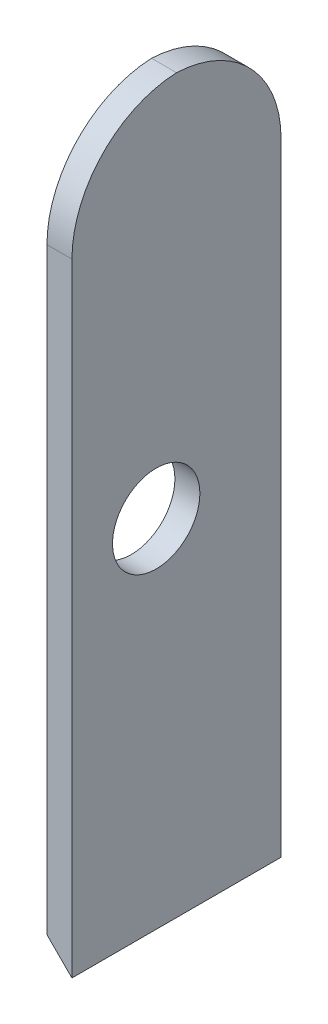
SolidWorks part; units mm, degrees
ref_plane "Front Plane" through (0, 0, 0) normal (0, 0, 1) x (1, 0, 0)
ref_plane "Top Plane" through (0, 0, 0) normal (0, 1, 0) x (1, 0, 0)
ref_plane "Right Plane" through (0, 0, 0) normal (1, 0, 0) x (0, 0, -1)
sketch "Sketch2" plane through (0, 0, 0) normal (1, 0, 0) x (0, 0, -1)
  line L1 (3.35, -11.75) -> (-3.35, -11.75)
  line L2 (3.35, -11.75) -> (3.35, 11.75)
  line L3 (3.35, 11.75) -> (-3.35, 11.75)
  line L4 (-3.35, -11.75) -> (-3.35, 11.75)
  line L5 (3.35, -11.75) -> (-3.35, 11.75) construction
  line L6 (3.35, 11.75) -> (-3.35, -11.75) construction
  point P1 (0, 0)
  dimension "D1" = 23.5
  dimension "D2" = 6.7
extrude "Boss-Extrude2" add sketch "Sketch2" along normal blind 0.8
chamfer "Chamfer1" distance 0.85 angle 45 1 edges at (0, -11.75, 0)
fillet "Fillet2" radius 3.5 2 edges at (0.4, 11.75, -3.35) (0.4, 11.75, 3.35)
sketch "Sketch6" plane through (0.8, 0, 0) normal (1, 0, 0) x (0, 0, -1)
  line L0 (-3.35, -11.7) -> (3.35, -11.7) construction
  circle A0 centre (-0.65, -0.3) radius 1.4
  arc A1 (0, 11.7468) -> (-3.35, 8.25) centre (0.15, 8.25) ccw construction
  dimension "D1" = 2.8
  dimension "D2" = 11.4
  dimension "D3" = 2.7
  dimension "D4" = 3.5
extrude "Cut-Extrude1" cut sketch "Sketch6" against normal blind 0.8
